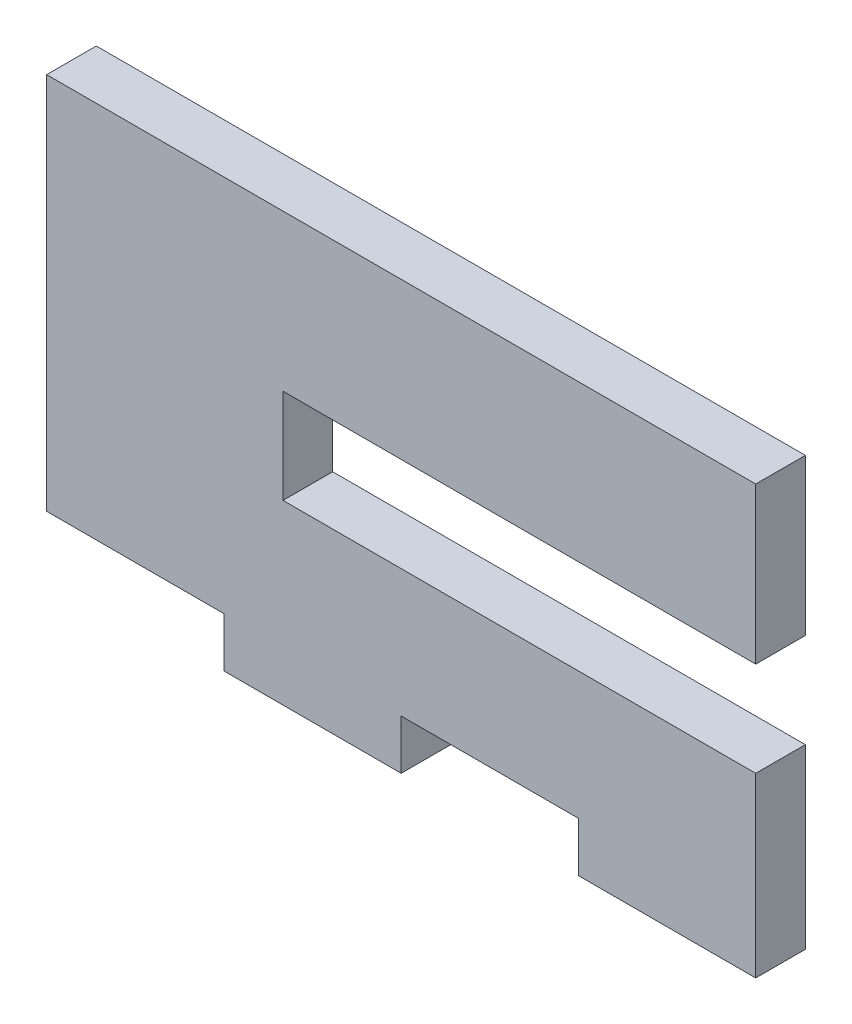
SolidWorks part; units mm, degrees
ref_plane "Front Plane" through (0, 0, 0) normal (0, 0, 1) x (1, 0, 0)
ref_plane "Top Plane" through (0, 0, 0) normal (0, 1, 0) x (1, 0, 0)
ref_plane "Right Plane" through (0, 0, 0) normal (1, 0, 0) x (0, 0, -1)
sketch "Sketch1" plane through (0, 0, 0) normal (0, 0, 1) x (1, 0, 0)
  line L1 (-382.8807, 285.7457) -> (-306.6807, 285.7457)
  line L2 (-382.8807, 285.7457) -> (-382.8807, 239.7717)
  line L3 (-382.8807, 239.7717) -> (-306.6807, 239.7717)
  line L4 (-306.6807, 285.7457) -> (-306.6807, 239.7717)
  dimension "D1" = 76.2
  dimension "D2" = 45.974
extrude "Boss-Extrude1" add sketch "Sketch1" along normal blind 5.334
sketch "Sketch2" plane through (0, 0, 5.334) normal (0, 0, 1) x (1, 0, 0)
  line L0 (-382.8807, 239.7717) -> (-306.6807, 239.7717) construction
  line L1 (-382.8807, 239.7717) -> (-363.8307, 239.7717)
  line L2 (-382.8807, 239.7717) -> (-382.8807, 245.1057)
  line L3 (-382.8807, 245.1057) -> (-363.8307, 245.1057)
  line L4 (-363.8307, 239.7717) -> (-363.8307, 245.1057)
  line L5 (-344.7807, 239.7717) -> (-325.7307, 239.7717)
  line L6 (-344.7807, 239.7717) -> (-344.7807, 245.1057)
  line L7 (-344.7807, 245.1057) -> (-325.7307, 245.1057)
  line L8 (-325.7307, 239.7717) -> (-325.7307, 245.1057)
  line L9 (-363.8307, 245.1057) -> (-344.7807, 245.1057) construction
  line L10 (-325.7307, 245.1057) -> (-306.6807, 245.1057) construction
  line L11 (-306.6807, 239.7717) -> (-306.6807, 285.7457) construction
  dimension "D1" = 5.334
extrude "Cut-Extrude1" cut sketch "Sketch2" against normal through all
sketch "Sketch3" plane through (0, 0, 0) normal (0, 0, -1) x (-1, 0, 0)
  line L0 (306.6807, 239.7717) -> (306.6807, 285.7457) construction
  line L1 (306.6807, 268.9817) -> (357.4807, 268.9817)
  line L2 (306.6807, 268.9817) -> (306.6807, 258.8217)
  line L3 (306.6807, 258.8217) -> (357.4807, 258.8217)
  line L4 (357.4807, 268.9817) -> (357.4807, 258.8217)
  line L5 (363.8307, 239.7717) -> (344.7807, 239.7717) construction
  dimension "D1" = 19.05
  dimension "D2" = 10.16
  dimension "D3" = 50.8
extrude "Cut-Extrude2" cut sketch "Sketch3" against normal through all
equation "\"MDF\"= .21in"
equation "\"Foamcore\"= .13in"
equation "\"Gmaterial\"= \"MDF\""
equation "\"D1@Boss-Extrude1\"=\"MDF\""
equation "\"D1@Sketch2\"=\"MDF\""
equation "\"D2@Sketch1\"=\"MDF\"+1.6"
